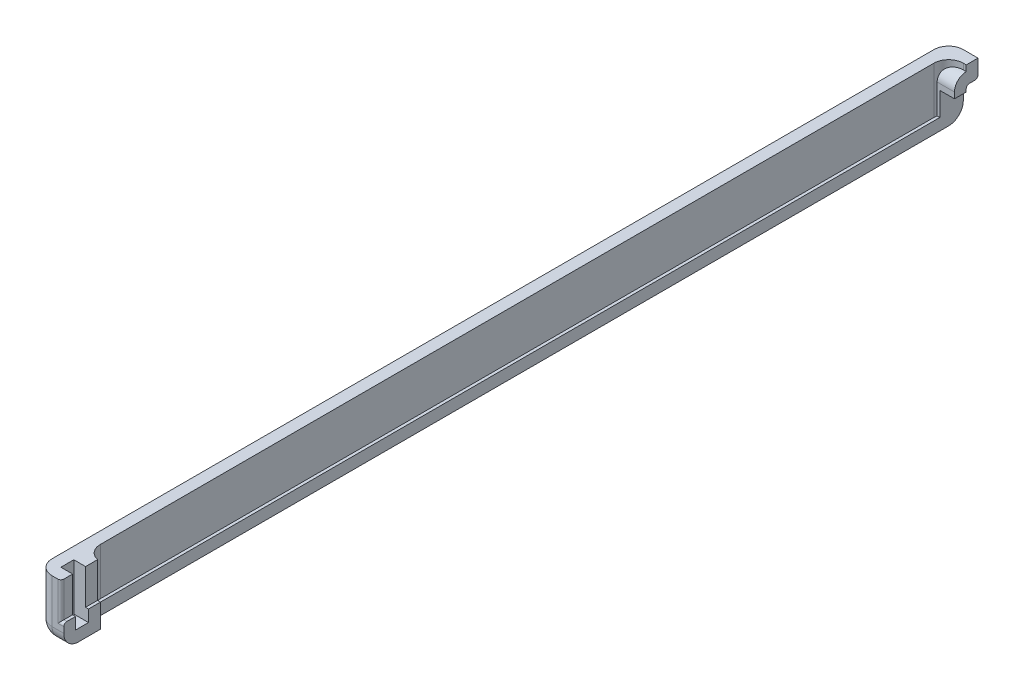
SolidWorks part; units mm, degrees
ref_plane "Front Plane" through (0, 0, 0) normal (0, 0, 1) x (1, 0, 0)
ref_plane "Top Plane" through (0, 0, 0) normal (0, 1, 0) x (1, 0, 0)
ref_plane "Right Plane" through (0, 0, 0) normal (1, 0, 0) x (0, 0, -1)
sketch "Sketch1" plane through (0, 0, 0) normal (0, 1, 0) x (1, 0, 0)
  line L1 (-19.5, 77.5) -> (19.5, 77.5)
  line L2 (-19.5, 77.5) -> (-19.5, -77.5)
  line L3 (-19.5, -77.5) -> (19.5, -77.5)
  line L4 (19.5, 77.5) -> (19.5, -77.5)
  line L5 (-19.5, 77.5) -> (19.5, -77.5) construction
  line L6 (-19.5, -77.5) -> (19.5, 77.5) construction
  point P0 (0, 0)
  dimension "D1" = 39
  dimension "D2" = 155
extrude "Boss-Extrude1" add sketch "Sketch1" along normal blind 2
sketch "Sketch2" plane through (0, 2, 0) normal (0, 1, 0) x (1, 0, 0)
  line L0 (-17.5, -75.5) -> (-17.5, -77.5)
  line L1 (-19.5, 77.5) -> (19.5, 77.5)
  line L2 (-19.5, 77.5) -> (-19.5, -77.5)
  line L3 (-19.5, -77.5) -> (19.5, -77.5)
  line L4 (19.5, 77.5) -> (19.5, -77.5)
  line L5 (-17.5, 75.5) -> (17.5, 75.5)
  line L6 (-17.5, 75.5) -> (-17.5, -75.5)
  line L7 (-17.5, -75.5) -> (17.5, -75.5)
  line L8 (17.5, 75.5) -> (17.5, -75.5)
  line L9 (-17.5, 75.5) -> (17.5, -75.5) construction
  line L10 (-17.5, -75.5) -> (17.5, 75.5) construction
  line L11 (17.5, -75.5) -> (17.5, -77.5)
  point P6 (0, 0)
  line M9 (19.5, -77.5) -> (19.5, 77.5)
  line M10 (19.5, 77.5) -> (-19.5, 77.5)
  line M11 (-19.5, 77.5) -> (-19.5, -77.5)
  line M12 (-19.5, -77.5) -> (19.5, -77.5)
  dimension "D1" = 2
  dimension "D2" = 2
extrude "Boss-Extrude2" add sketch "Sketch2" along normal blind 38 contours L8 L11 L3 L0 L6 L5 M9 M10 M11 M12 region at (-19.0983, 2, 76.5)
sketch "Sketch3" plane through (0, 2, 0) normal (0, 1, 0) x (1, 0, 0)
  line L0 (-17.5, 75.5) -> (-17.5, -77.5) construction
  line L1 (-17.5, -77.5) -> (-15.5, -77.5)
  line L2 (-17.5, -77.5) -> (-17.5, -75.5)
  line L3 (-17.5, -75.5) -> (-15.5, -75.5)
  line L4 (-15.5, -77.5) -> (-15.5, -75.5)
  line L5 (-17.5, -73.3) -> (-15.5, -73.3)
  line L6 (-17.5, -73.3) -> (-17.5, -71.3)
  line L7 (-17.5, -71.3) -> (-15.5, -71.3)
  line L8 (-15.5, -73.3) -> (-15.5, -71.3)
  line L9 (17.5, 75.5) -> (17.5, -77.5) construction
  line L10 (17.5, -77.5) -> (15.5, -77.5)
  line L11 (17.5, -77.5) -> (17.5, -75.5)
  line L12 (17.5, -75.5) -> (15.5, -75.5)
  line L13 (15.5, -77.5) -> (15.5, -75.5)
  line L14 (17.5, -73.3) -> (15.5, -73.3)
  line L15 (17.5, -73.3) -> (17.5, -71.3)
  line L16 (17.5, -71.3) -> (15.5, -71.3)
  line L17 (15.5, -73.3) -> (15.5, -71.3)
  line L18 (15.5, -75.5) -> (15.5, -73.3) construction
  line L19 (-15.5, -73.3) -> (15.5, -73.3) construction
  line L20 (-15.5, -75.5) -> (-15.5, -73.3) construction
  line L21 (-15.5, -75.5) -> (15.5, -75.5) construction
  line L22 (15.5, -71.3) -> (-15.5, -71.3) construction
  dimension "D1" = 2
  dimension "D2" = 2
  dimension "D3" = 2.2
  dimension "D4" = 2
extrude "Boss-Extrude3" add sketch "Sketch3" along normal up to surface (38 mm away) up to face at (0, 40, 0.5)
sketch "Sketch4" plane through (0, 0, -75.5) normal (0, 0, 1) x (1, 0, 0)
  line L0 (-17.5, 40) -> (-15.5, 40)
  line L1 (-17.5, 40) -> (17.5, 40) construction
  line L2 (-15.5, 40) -> (-15.5, 38)
  line L3 (-15.5, 38) -> (-17.5, 38)
  line L5 (-17.5, 38) -> (-17.5, 40)
  line L7 (-17.5, 40) -> (-17.5, 2) construction
  line L8 (-15.5, 33.8) -> (-17.5, 31.8)
  line L9 (-17.5, 31.8) -> (-17.5, 35.8)
  line L10 (-15.5, 33.8) -> (-15.5, 35.8)
  line L11 (-15.5, 35.8) -> (-17.5, 35.8)
  line L12 (0, 0) -> (0, 40) construction
  line L13 (15.5, 35.8) -> (17.5, 35.8)
  line L14 (15.5, 33.8) -> (15.5, 35.8)
  line L15 (17.5, 31.8) -> (17.5, 35.8)
  line L16 (15.5, 33.8) -> (17.5, 31.8)
  line L17 (17.5, 38) -> (17.5, 40)
  line L18 (15.5, 38) -> (17.5, 38)
  line L19 (15.5, 40) -> (15.5, 38)
  line L20 (17.5, 40) -> (15.5, 40)
  dimension "D1" = 2
  dimension "D2" = 2
  dimension "D3" = 45
  dimension "D4" = 2.2
  dimension "D5" = 2
extrude "Boss-Extrude4" add sketch "Sketch4" along normal up to surface (153 mm away) up to face at (0, 20.5, 77.5)
sketch "Sketch5" plane through (0, 2, 0) normal (0, 1, 0) x (1, 0, 0)
  line L1 (-15.5, -77.5) -> (15.5, -77.5)
  line L2 (-15.5, -77.5) -> (-15.5, -75.5)
  line L3 (-15.5, -75.5) -> (15.5, -75.5)
  line L4 (15.5, -77.5) -> (15.5, -75.5)
  line L5 (-15.5, -71.3) -> (15.5, -71.3)
  line L6 (-15.5, -71.3) -> (-15.5, -73.3)
  line L7 (-15.5, -73.3) -> (15.5, -73.3)
  line L8 (15.5, -71.3) -> (15.5, -73.3)
sketch "Sketch6" plane through (0, 0, -75.5) normal (0, 0, 1) x (1, 0, 0)
  line L0 (-17.5, 38) -> (-15.5, 38) construction
  line L1 (-17.5, 38) -> (17.5, 38)
  line L2 (-17.5, 38) -> (-17.5, 35.8)
  line L3 (-17.5, 35.8) -> (17.5, 35.8)
  line L4 (17.5, 38) -> (17.5, 35.8)
  line L5 (-17.5, 38) -> (-17.5, 35.8) construction
  line L6 (-15.5, 35.8) -> (-17.5, 35.8) construction
extrude "Cut-Extrude1" cut sketch "Sketch6" along normal through all
sketch "Sketch7" plane through (0, 2, 0) normal (0, 1, 0) x (1, 0, 0)
  line L1 (-17.5, -75.5) -> (17.5, -75.5)
  line L2 (-17.5, -75.5) -> (-17.5, -73.3)
  line L3 (-17.5, -73.3) -> (17.5, -73.3)
  line L4 (17.5, -75.5) -> (17.5, -73.3)
extrude "Cut-Extrude2" cut sketch "Sketch7" along normal through all
extrude "Boss-Extrude5" add sketch "Sketch5" along normal blind 2
sketch "Sketch8" plane through (0, 0, 0) normal (1, 0, 0) x (0, 0, -1)
  line L0 (75.5, 40) -> (73.5, 40)
  line L1 (-73.3, 40) -> (75.5, 40) construction
  line L2 (73.5, 40) -> (73.5, 38)
  line L3 (-73.3, 38) -> (75.5, 38) construction
  line L4 (73.5, 38) -> (75.5, 38)
  line L5 (75.5, 38) -> (75.5, 40)
  line L6 (75.5, 35.8) -> (73.5, 35.8)
  line L7 (-73.3, 35.8) -> (75.5, 35.8) construction
  line L8 (73.5, 35.8) -> (73.5, 33.8)
  line L9 (-71.3, 33.8) -> (75.5, 33.8) construction
  line L10 (73.5, 33.8) -> (75.5, 31.8)
  line L11 (75.5, 31.8) -> (75.5, 35.8)
  dimension "D1" = 2
extrude "Boss-Extrude6" add sketch "Sketch8" along normal up to surface and the other way up to surface up to face at (17.5, 16.9, -2.1) other way up to face at (-17.5, 16.9, -2.1)
sketch "Sketch10" plane through (-17.5, 0, 0) normal (1, 0, 0) x (0, 0, -1)
  line L1 (-75.5, 35.8) -> (-77.5, 35.8)
  line L2 (-75.5, 35.8) -> (-75.5, 38)
  line L3 (-75.5, 38) -> (-77.5, 38)
  line L4 (-77.5, 35.8) -> (-77.5, 38)
  line L5 (-73.3, 40) -> (-75.5, 40)
  line L6 (-73.3, 40) -> (-73.3, 38)
  line L7 (-73.3, 38) -> (-75.5, 38)
  line L8 (-75.5, 40) -> (-75.5, 38)
  line M1 (-75.5, 40) -> (-75.5, 38)
  line M2 (-75.5, 38) -> (-77.5, 38)
  line M3 (-77.5, 38) -> (-77.5, 35.8)
  line M4 (-77.5, 35.8) -> (-75.5, 35.8)
  line M11 (-73.3, 38) -> (-73.3, 40)
  line M12 (-73.3, 40) -> (-75.5, 40)
extrude "Boss-Extrude8" add sketch "Sketch10" along normal up to surface (2 mm away) contours L2 M4 M2 M3 | L7 M11 M12 M1 region at (-17.5, 39, 74.4) region at (-17.5, 36.9, 76.5) up to face at (-15.5, 39, -0.1)
sketch "Sketch11" plane through (17.5, 0, 0) normal (-1, 0, 0) x (0, 0, 1)
  line L1 (75.5, 35.8) -> (77.5, 35.8)
  line L2 (75.5, 35.8) -> (75.5, 38)
  line L3 (75.5, 38) -> (77.5, 38)
  line L4 (77.5, 35.8) -> (77.5, 38)
  line L5 (73.3, 40) -> (75.5, 40)
  line L6 (73.3, 40) -> (73.3, 38)
  line L7 (73.3, 38) -> (75.5, 38)
  line L8 (75.5, 40) -> (75.5, 38)
  line M2 (75.5, 35.8) -> (77.5, 35.8)
  line M3 (77.5, 35.8) -> (77.5, 38)
  line M4 (77.5, 38) -> (75.5, 38)
  line M5 (75.5, 38) -> (75.5, 40)
  line M6 (75.5, 40) -> (73.3, 40)
  line M7 (73.3, 40) -> (73.3, 38)
extrude "Boss-Extrude9" add sketch "Sketch11" along normal up to surface (2 mm away) contours L2 M2 M3 M4 | L7 M7 M5 M6 region at (17.5, 36.9, 76.5) region at (17.5, 39, 74.4) up to face at (15.5, 39, -0.1)
fillet "Fillet2" radius 2.5 17 edges at (-17.5, 16.9, 71.3) (17.5, 16.9, 71.3) (19.5, 20, 77.5) (-19.5, 20, 77.5) (-19.5, 20, -77.5) (-17.5, 16.9, -75.5) (17.5, 16.9, -75.5) (19.5, 20, -77.5) (-19.5, 40, 0) (0, 40, -77.5) (19.5, 40, 0) (0, 0, -77.5) (0, 0, 77.5) (-19.5, 0, 0) (19.5, 0, 0) (-17.5, 40, 77.5) (17.5, 40, 77.5)
sketch "Sketch13" plane through (0, 0, -77.5) normal (0, 0, -1) x (-1, 0, 0)
  line L0 (15.5, 37.5) -> (15.5, 4) construction
  line L1 (-15.5, 7) -> (15.5, 7)
  line L2 (-15.5, 7) -> (-15.5, 4)
  line L3 (-15.5, 4) -> (15.5, 4)
  line L4 (15.5, 7) -> (15.5, 4)
  dimension "D1" = 3
sketch "Sketch14" plane through (0, 0, -75.5) normal (0, 0, 1) x (1, 0, 0)
  line L1 (-18.25, 9) -> (18.25, 9)
  line L2 (-18.25, 9) -> (-18.25, 1.25)
  line L3 (-18.25, 1.25) -> (18.25, 1.25)
  line L4 (18.25, 9) -> (18.25, 1.25)
  line L5 (15.5, 7) -> (-15.5, 7) construction
  line L7 (17, 0) -> (17, 2.5) construction
  line L8 (19.5, 2.5) -> (17, 2.5) construction
  line L10 (-19.5, 2.5) -> (-17, 2.5) construction
  point P20 (17, 1.25)
  point P23 (18.25, 2.5)
  point P26 (-18.25, 2.5)
  dimension "D1" = 2
extrude "Boss-Extrude10" add sketch "Sketch14" along normal blind 2
extrude "Cut-Extrude4" cut sketch "Sketch13" against normal blind 2
fillet "Fillet3" radius 2 1 edges at (0, 9, -73.5)
fillet "Fillet4" radius 0.5 12 edges at (0, 4, -77.5) (0, 7, -77.5) (15.5, 7, -76.5) (15.5, 4, -76.5) (15.5, 5.5, -77.5) (-15.5, 4, -76.5) (-15.5, 7, -76.5) (-15.5, 5.5, -77.5) (0, 7, -75.5) (-15.5, 5.5, -75.5) (0, 4, -75.5) (15.5, 5.5, -75.5)
sketch "Sketch15" plane through (0, 0, 0) normal (0, -1, 0) x (1, 0, 0)
  line L0 (0, 77.5) -> (0, 0) construction
  line L1 (-17, 77.5) -> (17, 77.5) construction
  line L2 (0, 0) -> (0, -77.5) construction
  line L4 (17, -77.5) -> (-17, -77.5) construction
  circle A0 centre (0, 38.75) radius 5.1
  circle A1 centre (0, -38.75) radius 5.1
  dimension "D1" = 10.2
extrude "Cut-Extrude5" cut sketch "Sketch15" against normal through all
sketch "Sketch16" plane through (0, 2, 0) normal (0, 1, 0) x (1, 0, 0)
  circle A0 centre (0, 38.75) radius 7.1
  circle A1 centre (0, -38.75) radius 7.1
  circle A2 centre (0, 38.75) radius 5.1 construction
  dimension "D1" = 2
extrude "Boss-Extrude11" add sketch "Sketch16" along normal blind 1
fillet "Fillet5" radius 0.5 4 edges at (0, 2, 45.85) (0, 2, -31.65) (0, 3, 45.85) (0, 3, -31.65)
sketch "Sketch12" plane through (0, 0, -75.5) normal (0, 0, 1) x (1, 0, 0)
  line L0 (0, 0) -> (0, 40) construction
  line L1 (15.5, 40) -> (-15.5, 40) construction
  line L2 (0, 20) -> (-10, 20)
  line L3 (0, 20) -> (-9.0097, 15.6612)
  line L4 (0, 20) -> (-6.2349, 12.1817)
  line L5 (0, 20) -> (-2.2252, 10.2507)
  line L6 (0, 20) -> (2.2252, 10.2507)
  line L7 (0, 20) -> (6.2349, 12.1817)
  line L8 (0, 20) -> (9.0097, 15.6612)
  line L9 (0, 20) -> (10, 20)
  line L10 (0, 20) -> (9.0097, 24.3388)
  line L11 (0, 20) -> (6.2349, 27.8183)
  line L12 (0, 20) -> (2.2252, 29.7493)
  line L13 (0, 20) -> (-2.2252, 29.7493)
  line L14 (0, 20) -> (-6.2349, 27.8183)
  line L15 (0, 20) -> (-9.0097, 24.3388)
  circle A0 centre (0, 20) radius 10
  circle A1 centre (0, 20) radius 7.5
  circle A2 centre (0, 20) radius 5
  circle A3 centre (0, 20) radius 2.5
  point P26 (0, 20)
  dimension "D1" = 20
  dimension "D2" = 2.5
  dimension "D3" = 2.5
  dimension "D4" = 2.5
  dimension "D5" = 14
extrude "Cut-Extrude3" cut sketch "Sketch12" against normal through all contours A1 L6 A0 L7 | A1 L4 A0 L5 | A1 L2 A0 L3 | A1 L14 A0 L15 | A1 L0 A0 L13 | L0 A1 L12 A0 | A1 L10 A0 L11 | A1 L8 A0 L9 | A3 L8 A2 L9 | A3 L10 A2 L11 | L0 A3 L12 A2 | A3 L0 A2 L13 | A3 L14 A2 L15 | A3 L2 A2 L3 | A3 L4 A2 L5 | A3 L6 A2 L7 region at (-3.7903, 12.1293, -75.5) region at (3.7903, 12.1293, -75.5) region at (-1.6732, 16.5256, -75.5) region at (1.6732, 16.5256, -75.5) region at (-8.5168, 18.0561, -75.5) region at (8.5168, 18.0561, -75.5) region at (-0.4345, 23.8563, -75.5) region at (0.4345, 23.8563, -75.5) region at (-3.7596, 19.1419, -75.5) region at (3.7596, 19.1419, -75.5) region at (3.015, 22.4044, -75.5) region at (-3.015, 22.4044, -75.5) region at (-6.8299, 25.4467, -75.5) region at (6.8299, 25.4467, -75.5) region at (-0.9843, 28.7358, -75.5) region at (0.9843, 28.7358, -75.5)
fillet "Fillet6" radius 0.4 112 edges at (5.4555, 26.841, -77.5) (7.8183, 26.2349, -77.5) (7.8835, 23.7965, -77.5) (5.8637, 24.6762, -77.5) (3.75, 20, -77.5) (4.8746, 18.8874, -77.5) (3.3786, 18.3729, -77.5) (2.4373, 19.4437, -77.5) (-1.9471, 28.5306, -77.5) (0, 30, -77.5) (1.9471, 28.5306, -77.5) (0, 27.5, -77.5) (-7.8835, 16.2035, -77.5) (-9.7493, 17.7748, -77.5) (-8.75, 20, -77.5) (-7.312, 18.3311, -77.5) (2.3381, 17.0681, -77.5) (2.1694, 15.4952, -77.5) (0.8345, 16.344, -77.5) (1.0847, 17.7476, -77.5) (-0.8345, 16.344, -77.5) (-2.1694, 15.4952, -77.5) (-2.3381, 17.0681, -77.5) (-1.0847, 17.7476, -77.5) (5.4555, 13.159, -77.5) (4.3388, 10.9903, -77.5) (1.9471, 11.4694, -77.5) (3.2541, 13.2427, -77.5) (0, 22.5, -77.5) (-0.8345, 23.656, -77.5) (0, 25, -77.5) (0.8345, 23.656, -77.5) (-3.3786, 21.6271, -77.5) (-3.9092, 23.1174, -77.5) (-2.3381, 22.9319, -77.5) (-1.9546, 21.5587, -77.5) (-3.3786, 18.3729, -77.5) (-4.8746, 18.8874, -77.5) (-3.75, 20, -77.5) (-2.4373, 19.4437, -77.5) (-1.9471, 11.4694, -77.5) (-4.3388, 10.9903, -77.5) (-5.4555, 13.159, -77.5) (-3.2541, 13.2427, -77.5) (-7.8835, 23.7965, -77.5) (-7.8183, 26.2349, -77.5) (-5.4555, 26.841, -77.5) (-5.8637, 24.6762, -77.5) (2.3381, 22.9319, -77.5) (3.9092, 23.1174, -77.5) (3.3786, 21.6271, -77.5) (1.9546, 21.5587, -77.5) (8.75, 20, -77.5) (9.7493, 17.7748, -77.5) (7.8835, 16.2035, -77.5) (7.312, 18.3311, -77.5) (7.8835, 23.7965, -75.5) (7.8183, 26.2349, -75.5) (5.4555, 26.841, -75.5) (5.8637, 24.6762, -75.5) (3.3786, 18.3729, -75.5) (4.8746, 18.8874, -75.5) (3.75, 20, -75.5) (2.4373, 19.4437, -75.5) (1.9471, 28.5306, -75.5) (0, 30, -75.5) (-1.9471, 28.5306, -75.5) (0, 27.5, -75.5) (-8.75, 20, -75.5) (-9.7493, 17.7748, -75.5) (-7.8835, 16.2035, -75.5) (-7.312, 18.3311, -75.5) (0.8345, 16.344, -75.5) (2.1694, 15.4952, -75.5) (2.3381, 17.0681, -75.5) (1.0847, 17.7476, -75.5) (-2.3381, 17.0681, -75.5) (-2.1694, 15.4952, -75.5) (-0.8345, 16.344, -75.5) (-1.0847, 17.7476, -75.5) (1.9471, 11.4694, -75.5) (4.3388, 10.9903, -75.5) (5.4555, 13.159, -75.5) (3.2541, 13.2427, -75.5) (0, 22.5, -75.5) (0.8345, 23.656, -75.5) (0, 25, -75.5) (-0.8345, 23.656, -75.5) (-2.3381, 22.9319, -75.5) (-3.9092, 23.1174, -75.5) (-3.3786, 21.6271, -75.5) (-1.9546, 21.5587, -75.5) (-3.75, 20, -75.5) (-4.8746, 18.8874, -75.5) (-3.3786, 18.3729, -75.5) (-2.4373, 19.4437, -75.5) (-5.4555, 13.159, -75.5) (-4.3388, 10.9903, -75.5) (-1.9471, 11.4694, -75.5) (-3.2541, 13.2427, -75.5) (-5.4555, 26.841, -75.5) (-7.8183, 26.2349, -75.5) (-7.8835, 23.7965, -75.5) (-5.8637, 24.6762, -75.5) (3.3786, 21.6271, -75.5) (3.9092, 23.1174, -75.5) (2.3381, 22.9319, -75.5) (7.8835, 16.2035, -75.5) (9.7493, 17.7748, -75.5) (8.75, 20, -75.5) (7.312, 18.3311, -75.5) (1.9546, 21.5587, -75.5)
fillet "Fillet7" radius 0.5 8 edges at (15.5, 40, 0.75) (15.5, 39.2678, 76.7678) (-15.5, 40, 0.75) (-15.5, 39.2678, 76.7678) (0, 40, -73.5) (15.5, 20.75, 77.5) (-15.5, 20.75, 77.5) (0, 4, 77.5)
sketch "Sketch17" plane through (0, 0, 0) normal (0, -1, 0) x (1, 0, 0)
  line L0 (-17, -77.5) -> (-17, 70.3)
  line L1 (-17, -77.5) -> (17, -77.5)
  line L2 (17, -77.5) -> (17, 70.3)
  line L3 (17, -75) -> (17, 75) construction
  line L5 (17, 70.3) -> (15, 71.3)
  line L6 (15, 71.3) -> (15, 77.5)
  line L7 (15, 77.5) -> (-15, 77.5)
  line L8 (-15, 77.5) -> (-15, 71.3)
  line L9 (-15, 71.3) -> (-17, 70.3)
  line L10 (-17, 75) -> (-17, -75) construction
  line L12 (-15, 71.3) -> (15, 71.3) construction
  line L13 (17, 70.3) -> (-17, 70.3) construction
  line L14 (0, 71.3) -> (0, 77.5) construction
  line L15 (-17, 77.5) -> (17, 77.5) construction
  arc A0 (-19.5, -75) -> (-17, -77.5) centre (-17, -75) ccw construction
  dimension "D1" = 1
  dimension "D2" = 30
  dimension "D3" = 6.2
extrude "Cut-Extrude6" cut sketch "Sketch17" against normal blind 6
sketch "Sketch18" plane through (0, 0, 0) normal (0, 0, 1) x (1, 0, 0)
  line L0 (15, 9) -> (-15, 9) construction
  line L1 (-14.5, 9) -> (14.5, 9)
  line L2 (-14.5, 9) -> (-14.5, 6)
  line L3 (-14.5, 6) -> (14.5, 6)
  line L4 (14.5, 9) -> (14.5, 6)
  line L5 (-17, 6) -> (17, 6) construction
  line L6 (0, 6) -> (0, 0) construction
  dimension "D1" = 29
extrude "Cut-Extrude8" cut sketch "Sketch18" against normal through all
sketch "Sketch20" plane through (0, 0, 0) normal (0, 0, 1) x (1, 0, 0)
  line L0 (-16, 40) -> (16, 40) construction
  line L1 (-19.5, 40) -> (-14.5, 40)
  line L2 (-19.5, 40) -> (-19.5, 0)
  line L3 (-19.5, 0) -> (-14.5, 0)
  line L4 (-14.5, 40) -> (-14.5, 0)
  line L5 (-14.5, 6) -> (14.5, 6)
  line L6 (-14.5, 6) -> (-14.5, 40)
  line L7 (-14.5, 40) -> (14.5, 40)
  line L8 (14.5, 6) -> (14.5, 40)
  line L9 (14.5, 40) -> (19.5, 40)
  line L10 (14.5, 40) -> (14.5, 0)
  line L11 (14.5, 0) -> (19.5, 0)
  line L12 (19.5, 40) -> (19.5, 0)
  line L13 (-15, 0) -> (-17, 0) construction
  line L14 (-19.5, 2.5) -> (-19.5, 37.5) construction
  line L15 (17, 0) -> (15, 0) construction
  line L16 (19.5, 37.5) -> (19.5, 2.5) construction
extrude "Cut-Extrude11" cut sketch "Sketch20" against normal through all both and the other way through all contours L5 L8 L7 L4 | L12 L9 L8 L10 L11 region at (0, 23, 0) region at (17, 20, 0)
sketch "Sketch21" plane through (0, 0, 0) normal (1, 0, 0) x (0, 0, -1)
  line L0 (77.5, 37.5) -> (77.5, 7.5) construction
  line L1 (-77.5, 40) -> (77.5, 40)
  line L2 (-77.5, 40) -> (-77.5, 30)
  line L3 (-77.5, 30) -> (77.5, 30)
  line L4 (77.5, 40) -> (77.5, 30)
  line L5 (77.5, 30) -> (-77.5, 30)
  line L6 (77.5, 30) -> (77.5, 10)
  line L7 (77.5, 10) -> (-77.5, 10)
  line L8 (-77.5, 30) -> (-77.5, 10)
  line L9 (-77.5, 10) -> (77.5, 10)
  line L10 (-77.5, 10) -> (-77.5, 0)
  line L11 (-77.5, 0) -> (77.5, 0)
  line L12 (77.5, 10) -> (77.5, 0)
  line L13 (-70.3, 0) -> (75, 0) construction
  line L14 (-77.5, 3.5) -> (-77.5, 2.5) construction
  line L15 (-75, 40) -> (74, 40) construction
  line L16 (77.5, 30) -> (77.5, 10)
  line L17 (-77.5, 10) -> (-77.5, 30)
  dimension "D1" = 20
  dimension "D2" = 10
extrude "Cut-Extrude12" cut sketch "Sketch21" against normal through all contours L3 L8 L7 L6 | L4 L1 L2 L3 region at (0, 35, 0) region at (0, 20, 0)
